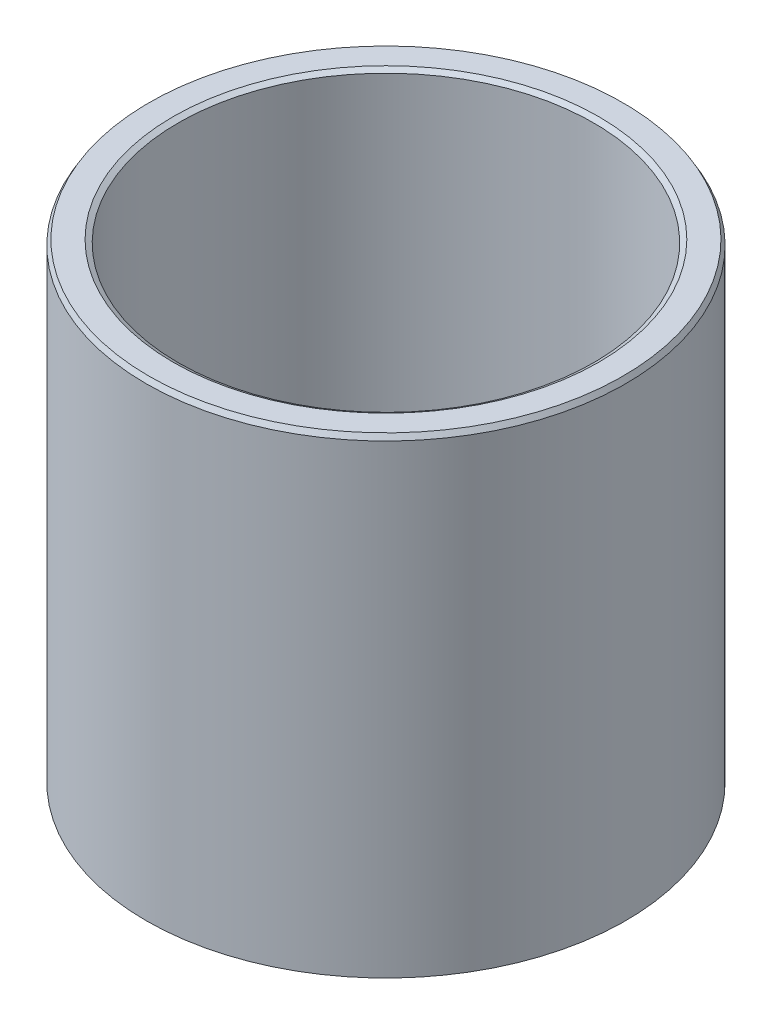
SolidWorks part; units mm, degrees
ref_plane "Front Plane" through (0, 0, 0) normal (0, 0, 1) x (1, 0, 0)
ref_plane "Top Plane" through (0, 0, 0) normal (0, 1, 0) x (1, 0, 0)
ref_plane "Right Plane" through (0, 0, 0) normal (1, 0, 0) x (0, 0, -1)
sketch "Sketch1" plane through (0, 0, 0) normal (0, 1, 0) x (1, 0, 0)
  circle A0 centre (0, 0) radius 57.5
  dimension "SLEEVE_OD" = 115
extrude "Boss-Extrude1" add sketch "Sketch1" along normal blind 113.4111
sketch "Sketch2" plane through (0, 0, 0) normal (0, 1, 0) x (1, 0, 0)
  circle A0 centre (0, 0) radius 49.8062
  dimension "BORE_D" = 99.6124
extrude "Cut-Extrude1" cut sketch "Sketch2" along normal through all
chamfer "Chamfer1" distance 1.2084 angle 30 4 edges at (0, 113.4111, 49.8062) (0, 0, 49.8062) (0, 0, 57.5) (0, 113.4111, 57.5) first distance on face at (0, 113.4111, 49.8062) first distance on face at (0, 0, 49.8062) first distance on face at (0, 113.4111, 57.5)
